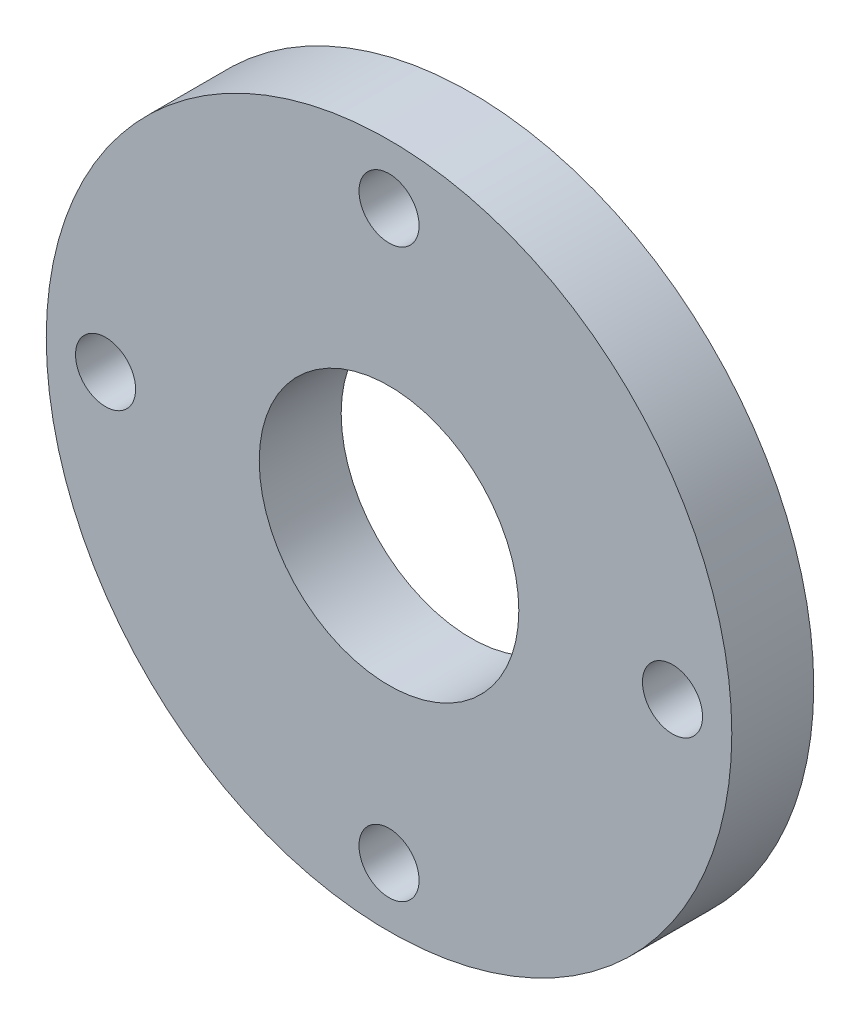
SolidWorks part; units mm, degrees
material "6061-T6 (SS)"
ref_plane "Front Plane" through (0, 0, 0) normal (0, 0, 1) x (1, 0, 0)
ref_plane "Top Plane" through (0, 0, 0) normal (0, 1, 0) x (1, 0, 0)
ref_plane "Right Plane" through (0, 0, 0) normal (1, 0, 0) x (0, 0, -1)
sketch "Sketch1" plane through (0, 0, 0) normal (1, 0, 0) x (0, 0, -1)
  line L0 (-95.847, -9.5) -> (-164, -9.5)
  line L5 (-1000, 0) -> (49000, 0)
  line L6 (0, -9.5) -> (0, 9.5)
  line L13 (0, 9.5) -> (-45.847, 9.5)
  line L26 (-45.847, 9.5) -> (-45.847, 14)
  line L27 (-45.847, 14) -> (-95.847, 14)
  line L32 (-95.847, 14) -> (-95.847, 9.5)
  line L34 (-180, 7) -> (-180, -7)
  line L36 (-95.847, -9.5) -> (-95.847, -14)
  line L37 (-95.847, -14) -> (-45.847, -14)
  line L38 (-45.847, -14) -> (-45.847, -9.5)
  line L39 (0, -9.5) -> (-45.847, -9.5)
  line L40 (-25.305, 37.6491) -> (-16.305, 37.6491)
  line L41 (-111.341, 22.6187) -> (-95.847, 22.6187)
  line L42 (-111.341, 22.6187) -> (-111.341, -22.6187)
  line L43 (-111.341, -22.6187) -> (-95.847, -22.6187)
  line L44 (-95.847, 22.6187) -> (-95.847, -22.6187)
  line L45 (-111.341, 22.6187) -> (-95.847, -22.6187) construction
  line L46 (-111.341, -22.6187) -> (-95.847, 22.6187) construction
  line L47 (-30.353, 22.6187) -> (-45.847, 22.6187)
  line L48 (-30.353, 22.6187) -> (-30.353, -22.6187)
  line L49 (-30.353, -22.6187) -> (-45.847, -22.6187)
  line L50 (-45.847, 22.6187) -> (-45.847, -22.6187)
  line L51 (-30.353, 22.6187) -> (-45.847, -22.6187) construction
  line L52 (-30.353, -22.6187) -> (-45.847, 22.6187) construction
  line L59 (-16.305, 37.6491) -> (-16.305, -37.6491)
  line L60 (-16.305, -37.6491) -> (-25.305, -37.6491)
  line L61 (-25.305, -22.6187) -> (-27.305, -22.6187)
  line L62 (-27.305, -22.6187) -> (-27.305, -12.5)
  line L63 (-27.305, -12.5) -> (-25.305, -12.5)
  line L64 (-25.305, -12.5) -> (-25.305, 12.5)
  line L65 (-25.305, 12.5) -> (-27.305, 12.5)
  line L66 (-27.305, 12.5) -> (-27.305, 22.6187)
  line L67 (-27.305, 22.6187) -> (-25.305, 22.6187)
  line L68 (-25.305, 22.6187) -> (-25.305, 37.6491)
  line L69 (-25.305, -22.6187) -> (-25.305, -37.6491)
  line L71 (-119.469, 37.6491) -> (-26.305, 37.6491)
  line L72 (-119.469, 37.6491) -> (-119.469, -37.6491)
  line L73 (-119.469, -37.6491) -> (-26.305, -37.6491)
  line L74 (-26.305, 37.6491) -> (-26.305, -37.6491)
  line L75 (-119.469, 37.6491) -> (-26.305, -37.6491) construction
  line L76 (-119.469, -37.6491) -> (-26.305, 37.6491) construction
  line L77 (-164, -9.5) -> (-164, -7)
  line L78 (-164, -7) -> (-180, -7)
  line L79 (-95.847, 9.5) -> (-164, 9.5)
  line L80 (-164, 7) -> (-180, 7)
  line L81 (-164, 9.5) -> (-164, 7)
  line L82 (-129.9235, 9.5) -> (-129.9235, -9.5) construction
  line L83 (-22.9235, 9.5) -> (-22.9235, -9.5) construction
  line L96 (-119.469, 37.6491) -> (-128.469, 37.6491)
  line L98 (-119.469, -37.6491) -> (-128.469, -37.6491)
  line L99 (-128.469, 37.6491) -> (-128.469, -37.6491)
  line L110 (-119.469, 37.6491) -> (-119.469, -37.6491)
  point P3 (0, 0)
  point P18 (-103.594, 0)
  point P24 (-38.1, 0)
  point P29 (-72.887, 0)
  point P48 (-16.305, 31.1339)
  point P70 (-128.469, 31.1339)
revolve "Main_body" add sketch "Sketch1" angle 360 about L5 region at (0, 23.5746, 123.969)
sketch "Sketch5" plane through (0, 0, 128.469) normal (0, 0, 1) x (1, 0, 0)
  circle A0 centre (0, 0) radius 14.2558
  dimension "D1" = 28.5115
extrude "seal_seat" cut sketch "Sketch5" against normal through all
hole_wizard "M6 Clearance Hole1" positions "Sketch3" profile "Sketch4" hole size "M6" standard "ANSI Metric" end condition through all
sketch "Sketch3" plane through (0, 0, 128.469) normal (0, 0, 1) x (1, 0, 0)
  point P0 (0, 31.1339)
sketch "Sketch4" plane through (0, 31.1339, 128.469) normal (1, 0, 0) x (0, -1, 0)
  line L0 (0, 0) -> (0, 9)
  line L1 (0, 9) -> (3.3, 9)
  line L2 (3.3, 9) -> (3.3, 0)
  line L5 (3.3, 0) -> (0, 0)
  line L11 (0, -6.35) -> (0, 107.95) construction
  dimension "Thru Hole Dia." = 6.6
  dimension "Thru Hole Depth" = 9
pattern_circular "CirPattern1" count 4 over 360 about axis through (0, 0, 1000) along (0, 0, -1) of "M6 Clearance Hole1"
